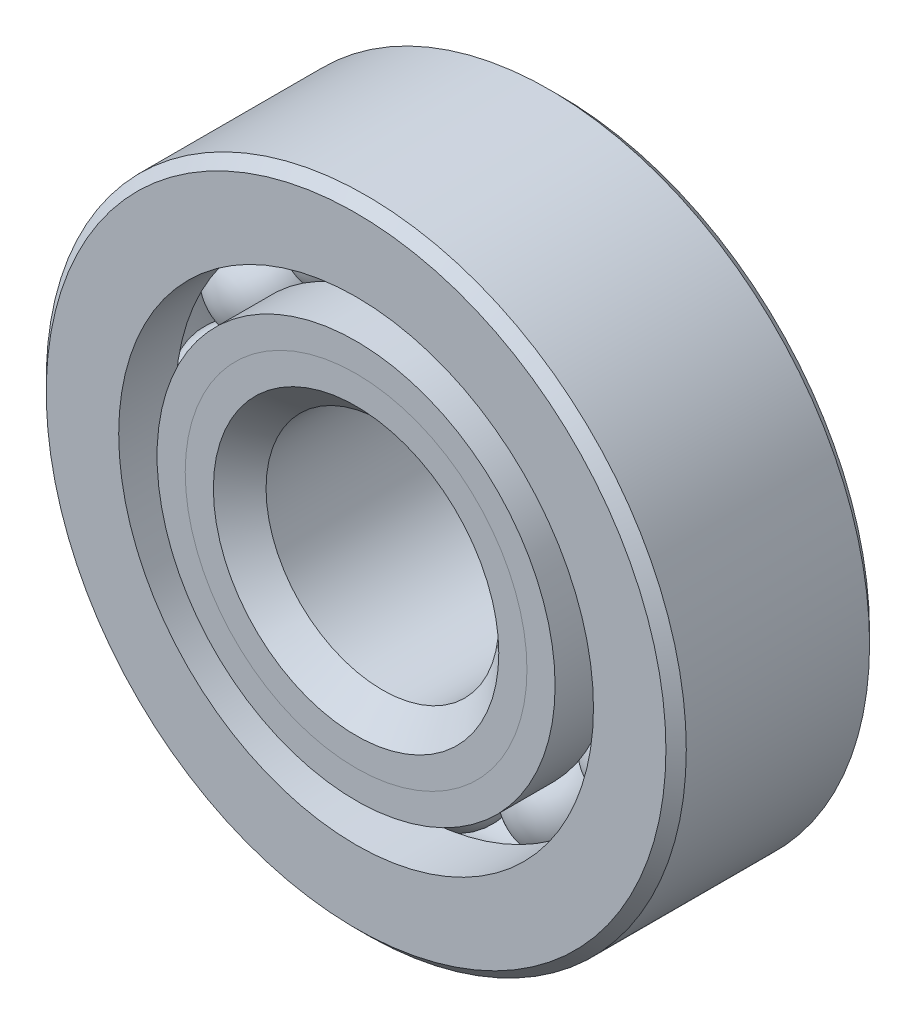
SolidWorks part; units mm, degrees
ref_plane "Front Plane" through (0, 0, 0) normal (0, 0, 1) x (1, 0, 0)
ref_plane "Top Plane" through (0, 0, 0) normal (0, 1, 0) x (1, 0, 0)
ref_plane "Right Plane" through (0, 0, 0) normal (1, 0, 0) x (0, 0, -1)
sketch "Sketch1" plane through (0, 0, 0) normal (1, 0, 0) x (0, 0, -1)
  line L0 (-5.5562, 0) -> (5.5562, 0) construction
  line L1 (0, 17.4625) -> (0, -17.4625) construction
  line L2 (5.0006, 17.4625) -> (-5.0006, 17.4625)
  line L3 (-5.0006, 17.4625) -> (-5.5563, 16.9069)
  line L4 (-5.5563, 16.9069) -> (-5.5563, 12.953)
  line L5 (-5.5563, 12.953) -> (-2.4694, 12.953)
  line L6 (5.5563, 12.953) -> (2.4694, 12.953)
  line L7 (5.5563, 16.9069) -> (5.5563, 12.953)
  line L8 (5.0006, 17.4625) -> (5.5563, 16.9069)
  line L9 (0, 17.4625) -> (0, 11.9062) construction
  line L10 (0, 11.9062) -> (0, 6.35) construction
  arc A0 (-2.4694, 12.953) -> (2.4694, 12.953) centre (0, 11.9062) cw
  point P14 (0, 6.35)
  dimension "D3" = 4.9389
  dimension "D1" = 45
  dimension "Width" = 11.1125
  dimension "OD" = 34.925
  dimension "D2" = 0.5556
  dimension "Shaft Dia" = 12.7
  dimension "D4" = 1.0467
revolve "Revolve1" add sketch "Sketch1" angle 360 about L0
sketch "Sketch2" plane through (0, 0, 0) normal (1, 0, 0) x (0, 0, -1)
  line L0 (-5.5563, 10.8595) -> (-2.4694, 10.8595)
  line L1 (-5.5563, 16.9069) -> (-5.5563, -16.9069) construction
  line L2 (-5.5563, 10.8595) -> (-5.5563, 9.3233)
  line L3 (-5.5563, 9.3233) -> (-4.02, 7.7871)
  line L4 (-4.02, 7.7871) -> (0, 7.7871)
  line L5 (0, 17.4625) -> (0, -17.4625) construction
  line L6 (0, 7.7871) -> (0, 9.2241)
  line L7 (0, 9.2241) -> (0, 6.35) construction
  line L8 (-5.5563, 10.8595) -> (-5.5563, 7.7871) construction
  line L9 (-5.5563, 7.7871) -> (-4.02, 7.7871) construction
  arc A0 (-2.4694, 10.8595) -> (0, 9.2241) centre (0, 11.9062) ccw
  arc A1 (2.4694, 12.953) -> (-2.4694, 12.953) centre (0, 11.9062) ccw construction
  circle A2 centre (0, 11.9062) radius 2.6821 construction
  dimension "D1" = 45
revolve "Revolve2" add sketch "Sketch2" angle 360 about L0
sketch "Sketch3" plane through (0, 0, 0) normal (1, 0, 0) x (0, 0, -1)
  line L0 (-5.5563, 9.3233) -> (-4.02, 7.7871)
  line L1 (-4.02, 7.7871) -> (0, 7.7871)
  line L2 (0, 7.7871) -> (0, 9.2241)
  line L3 (-5.5563, 9.3233) -> (-5.5563, 7.7871)
  line L4 (-5.5563, 10.8595) -> (-5.5563, 7.7871) construction
  line L5 (-5.5563, 7.7871) -> (-4.1192, 6.35)
  line L6 (-4.1192, 6.35) -> (5.0006, 6.35)
  line L7 (5.0006, 17.4625) -> (5.0006, -17.4625) construction
  line L8 (5.0006, 6.35) -> (5.5563, 6.9056)
  line L9 (5.5563, -16.9069) -> (5.5563, 16.9069) construction
  line L10 (5.5563, 6.9056) -> (5.5563, 10.8595)
  line L11 (5.5563, 10.8595) -> (2.4694, 10.8595)
  line L13 (5.0006, 17.4625) -> (5.5563, 16.9069) construction
  circle A0 centre (0, 11.9062) radius 2.6821 construction
  arc A1 (2.4694, 10.8595) -> (0, 9.2241) centre (0, 11.9062) cw
revolve "Revolve3" add sketch "Sketch3" angle 360 about L0
sketch "Sketch4" plane through (0, 0, 0) normal (1, 0, 0) x (0, 0, -1)
  line L0 (-2.6821, 11.9062) -> (2.6821, 11.9062)
  circle A1 centre (0, 11.9062) radius 2.6821 construction
  arc A2 (-2.6821, 11.9062) -> (2.6821, 11.9062) centre (0, 11.9062) cw
  arc A3 (2.4694, 12.953) -> (-2.4694, 12.953) centre (0, 11.9062) ccw construction
revolve "Revolve4" add sketch "Sketch4" angle 360 about L0
ref_axis "Axis1" through (0, 0, -5.5562) along (0, 0, 1)
pattern_circular "CirPattern1" count 12 every 30 about axis through (0, 0, -5.5562) along (0, 0, 1) of bodies 104
equation "\"D2@Sketch1\" = \"Width@Sketch1\"*.05"
equation "\"D3@Sketch1\" = \"Width@Sketch1\"/2.25"
equation "\"D4@Sketch1\" = (((\"OD@Sketch1\"-\"Width@Sketch1\")/2)/3.25)/3.5"
equation "\"D2@CirPattern1\" = 360/\"Balls@CirPattern1\""
